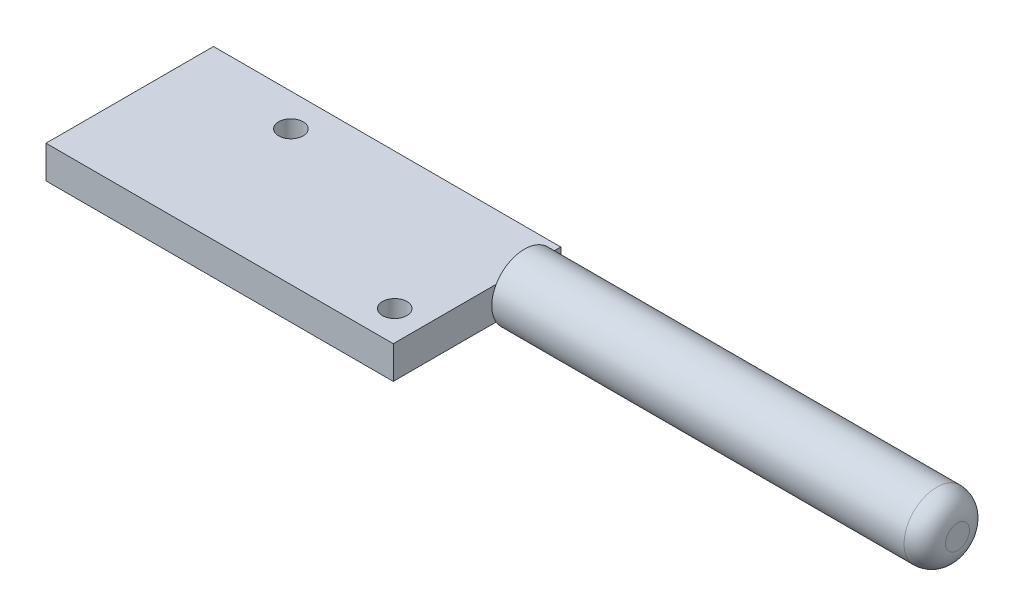
SolidWorks part; units mm, degrees
ref_plane "Front Plane" through (0, 0, 0) normal (0, 0, 1) x (1, 0, 0)
ref_plane "Top Plane" through (0, 0, 0) normal (0, 1, 0) x (1, 0, 0)
ref_plane "Right Plane" through (0, 0, 0) normal (1, 0, 0) x (0, 0, -1)
sketch "Sketch1" plane through (0, 0, 0) normal (0, 1, 0) x (1, 0, 0)
  line L1 (-21.25, -10.25) -> (21.25, -10.25)
  line L2 (-21.25, -10.25) -> (-21.25, 10.25)
  line L3 (-21.25, 10.25) -> (21.25, 10.25)
  line L4 (21.25, -10.25) -> (21.25, 10.25)
  line L5 (-21.25, -10.25) -> (21.25, 10.25) construction
  line L6 (-21.25, 10.25) -> (21.25, -10.25) construction
  point P0 (0, 0)
  dimension "D1" = 20.5
  dimension "D2" = 42.5
extrude "Boss-Extrude1" add sketch "Sketch1" along normal blind 4
sketch "Sketch2" plane through (21.25, 0, 0) normal (1, 0, 0) x (0, 0, -1)
  circle A0 centre (5.8044, 2) radius 4
extrude "Boss-Extrude2" add sketch "Sketch2" along normal blind 53
fillet "Fillet1" radius 2.54 1 edges at (74.25, 2, -9.8044)
sketch "Sketch4" plane through (0, 4, 0) normal (0, 1, 0) x (1, 0, 0)
  line L0 (-21.25, 10.25) -> (-21.25, -10.25) construction
  line L1 (-7.788, 6.26) -> (17.612, 6.26) construction
  line L2 (-7.788, 6.26) -> (-7.788, -6.44) construction
  line L3 (-7.788, -6.44) -> (17.612, -6.44) construction
  line L4 (17.612, 6.26) -> (17.612, -6.44) construction
  line L5 (-7.788, 6.26) -> (17.612, -6.44) construction
  line L6 (-7.788, -6.44) -> (17.612, 6.26) construction
  line L7 (-21.25, -10.25) -> (21.25, -10.25) construction
  circle A0 centre (17.612, -6.44) radius 1.5
  circle A1 centre (-7.788, 6.26) radius 1.5
  point P0 (4.912, -0.09)
  dimension "D5" = 3
  dimension "D6" = 3
  dimension "D1" = 12.7
  dimension "D2" = 25.4
  dimension "D3" = 13.462
  dimension "D4" = 3.81
extrude "Cut-Extrude2" cut sketch "Sketch4" against normal through all
